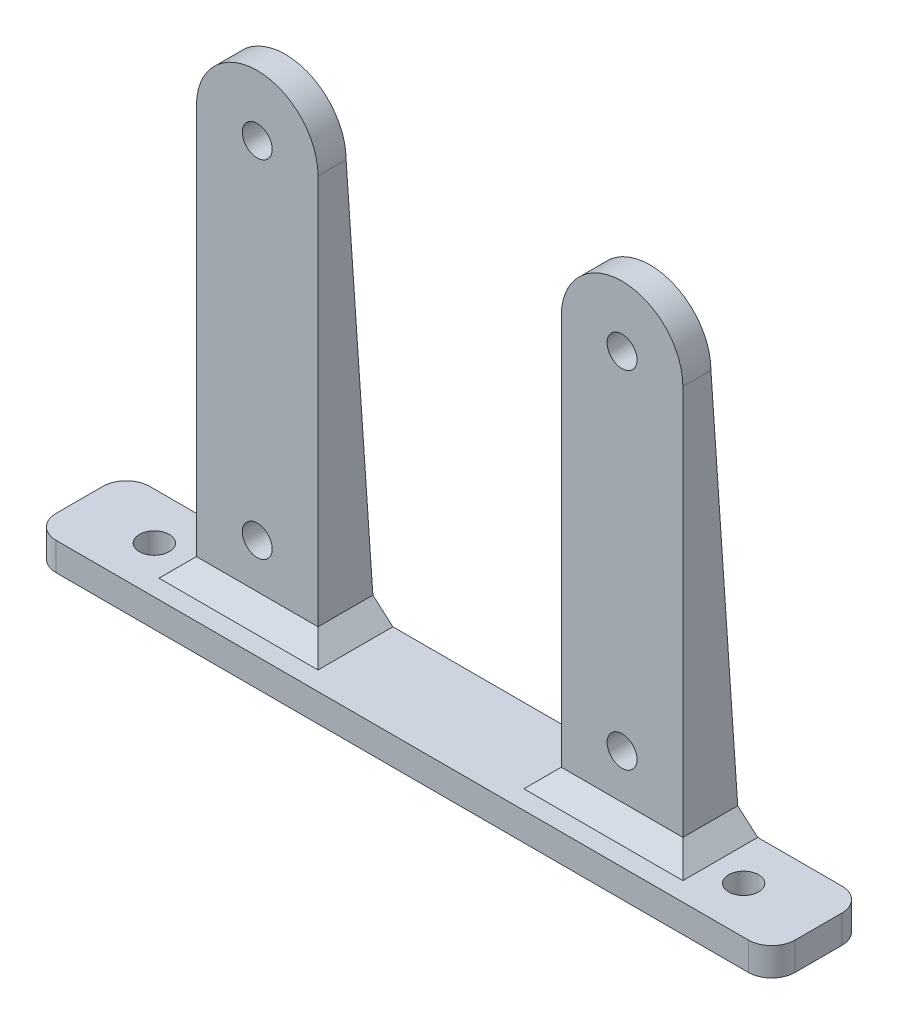
SolidWorks part; units mm, degrees
ref_plane "前视基准面" through (0, 0, 0) normal (0, 0, 1) x (1, 0, 0)
ref_plane "上视基准面" through (0, 0, 0) normal (0, 1, 0) x (1, 0, 0)
ref_plane "右视基准面" through (0, 0, 0) normal (1, 0, 0) x (0, 0, -1)
sketch "草图1" plane through (0, 0, 0) normal (0, 1, 0) x (1, 0, 0)
  line L1 (0, 0) -> (79, 0)
  line L2 (0, 0) -> (0, 10)
  line L3 (0, 10) -> (79, 10)
  line L4 (79, 0) -> (79, 10)
  dimension "D1" = 79
  dimension "D2" = 10
extrude "凸台-拉伸1" add sketch "草图1" along normal blind 3
sketch "草图2" plane through (0, 3, 0) normal (0, 1, 0) x (1, 0, 0)
  line L0 (-3.0519, 5) -> (42.0914, 5) construction
  line L1 (20, 10.6499) -> (20, -3.0532) construction
  line L2 (26.5, 7) -> (13.5, 7)
  line L3 (13.5, 7) -> (13.5, 4)
  line L4 (13.5, 4) -> (26.5, 4)
  line L5 (26.5, 7) -> (26.5, 4)
  line L6 (79, 10) -> (0, 10) construction
  line L7 (0, 10) -> (0, 0) construction
  point P9 (20, 4)
  point P10 (20, 7)
  dimension "D1" = 3
  dimension "D2" = 13
  dimension "D3" = 20
  dimension "D4" = 3
extrude "凸台-拉伸2" add sketch "草图2" along normal blind 43.75
sketch "草图4" plane through (0, 0, -4) normal (0, 0, 1) x (1, 0, 0)
  line L0 (13.5, 46.75) -> (26.5, 46.75) construction
  line L1 (13.5, 46.75) -> (26.5, 46.75)
  arc A0 (26.5, 46.75) -> (13.5, 46.75) centre (20, 46.75) ccw
extrude "凸台-拉伸3" add sketch "草图4" against normal blind 3
sketch "草图5" plane through (13.5, 0, 0) normal (-1, 0, 0) x (0, 0, 1)
  line L0 (-10, 3) -> (-7, 46.75)
rib "筋1" sketch "草图5" sketch "草图5" thickness 2 extrusion direction parallel to sketch draft on no parameters "D1"=2
sketch "草图7" plane through (26.5, 0, 0) normal (1, 0, 0) x (0, 0, -1)
  line L0 (7, 46.75) -> (10, 3)
rib "筋2" sketch "草图7" sketch "草图7" thickness 2 extrusion direction parallel to sketch draft on no parameters "D1"=2
sketch "草图8" plane through (0, 0, -4) normal (0, 0, 1) x (1, 0, 0)
  line L0 (20, -3.9148) -> (20, 53.1577) construction
  line L1 (13.5, 3) -> (26.5, 3) construction
  circle A0 centre (20, 9.75) radius 1.6
  circle A1 centre (20, 46.75) radius 1.6
  point P2 (20, 9.75)
  dimension "D1" = 6.75
extrude "切除-拉伸1" cut sketch "草图8" against normal blind 3
fillet "圆角1" radius 2.5 4 edges at (0, 1.5, -10) (79, 1.5, -10) (79, 1.5, 0) (0, 1.5, 0)
sketch "草图9" plane through (0, 3, 0) normal (0, 1, 0) x (1, 0, 0)
  line L0 (-2.5396, 5) -> (43.4041, 5) construction
  line L1 (0, 7.5) -> (0, 2.5) construction
  line L3 (79, 2.5) -> (79, 7.5) construction
  line L5 (76.5, 10) -> (26.5, 10) construction
  line L6 (2.5, 0) -> (76.5, 0) construction
  line L7 (39.5, 22.5235) -> (39.5, -16.253) construction
  circle A0 centre (8, 5) radius 1.6
  circle A3 centre (71, 5) radius 1.6
  dimension "D3" = 63
  dimension "D2" = 8
  dimension "D1" = 8
extrude "切除-拉伸5" cut sketch "草图9" against normal blind 3
chamfer "倒角2" distance 2 angle 45 3 edges at (20, 3, -4) (26.5, 3, -7) (13.5, 3, -7)
ref_plane "基准面1" through (39.5, 0, 0) normal (-1, 0, 0) x (0, 0, 1)
mirror "镜向1" about plane through (39.5, 0, 0) normal (-1, 0, 0) of "倒角2", "切除-拉伸1", "凸台-拉伸3", "凸台-拉伸2", "筋2", "筋1"
